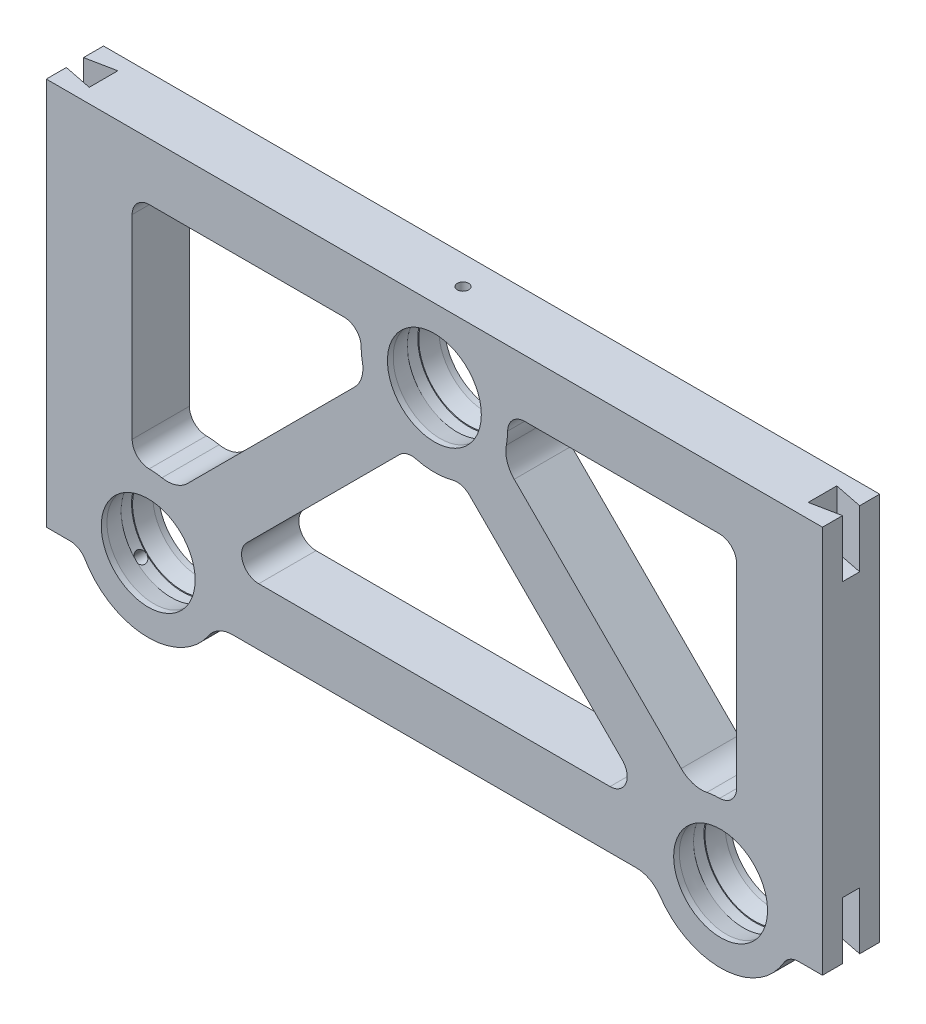
SolidWorks part; units mm, degrees
ref_plane "Front Plane" through (0, 0, 0) normal (0, 0, 1) x (1, 0, 0)
ref_plane "Top Plane" through (0, 0, 0) normal (0, 1, 0) x (1, 0, 0)
ref_plane "Right Plane" through (0, 0, 0) normal (1, 0, 0) x (0, 0, -1)
sketch "Sketch1" plane through (0, 0, 0) normal (0, 0, 1) x (1, 0, 0)
  line L0 (-26.538, 0) -> (73.462, 0) construction
  line L2 (-26.538, 0) -> (23.462, 50) construction
  line L3 (23.462, 50) -> (73.462, 0) construction
  line L4 (-14.755, 5) -> (61.679, 5)
  line L5 (-14.755, -5) -> (61.679, -5)
  line L6 (-21.7417, 11.8674) -> (11.5946, 45.2037)
  line L7 (18.6657, 38.1326) -> (-14.6706, 4.7963)
  line L8 (28.2583, 38.1326) -> (61.5946, 4.7963)
  line L9 (35.3294, 45.2037) -> (68.6657, 11.8674)
  circle A0 centre (23.462, 50) radius 8.2
  circle A1 centre (73.462, 0) radius 8.2
  circle A2 centre (-26.538, 0) radius 8.2
  circle A3 centre (-26.538, 0) radius 12.8
  circle A4 centre (23.462, 50) radius 12.8
  circle A5 centre (73.462, 0) radius 12.8
  dimension "D1" = 16.4
  dimension "D2" = 16.4
  dimension "D3" = 16.4
  dimension "D4" = 45
  dimension "D5" = 45
  dimension "D6" = 100
  dimension "D7" = 4.6
  dimension "D8" = 4.6
  dimension "D9" = 4.6
  dimension "D10" = 5
  dimension "D11" = 5
  dimension "D12" = 5
  dimension "D13" = 5
  dimension "D14" = 5
  dimension "D15" = 5
extrude "Boss-Extrude1" add sketch "Sketch1" along normal blind 8 contours A3 A2 | A4 L6 A3 L4 L7 | A4 A0 | A5 L9 A4 L8 L4 | A5 L8 L4 L7 A3 L5 | A5 A1 | A3 L7 L4 | A5 L4 L8
sketch3d "3DSketch1" plane through (0, 0, 0) normal (0, 0, 1) x (1, 0, 0)
  dimension "D1" = 4
sketch "Sketch3" plane through (0, 0, 4) normal (0, 0, 1) x (1, 0, 0)
  circle A0 centre (-26.538, 0) radius 8.9053
  circle A1 centre (23.462, 50) radius 8.9053
  circle A2 centre (73.462, 0) radius 8.9053
  circle A3 centre (-26.538, 0) radius 8.2 construction
  circle A4 centre (23.462, 50) radius 8.2 construction
  circle A5 centre (73.462, 0) radius 8.2 construction
  dimension "D1" = 0.7053
  dimension "D2" = 0.7053
  dimension "D3" = 0.7053
extrude "Cut-Extrude1" cut sketch "Sketch3" against normal blind 1 and the other way blind 1 contours A1 | A0 | A2
sketch3d "3DSketch2" plane through (0, 0, 0) normal (0, 0, 1) x (1, 0, 0)
sketch3d "3DSketch3" plane through (0, 0, 0) normal (0, 0, 1) x (1, 0, 0)
  dimension "D1" = 26
sketch "Sketch4" plane through (0, 63.2, 0) normal (0, -1, 0) x (-1, 0, 0)
  line L0 (-41.8, -4) -> (41.8, -4) construction
  line L1 (-86.262, 0) -> (-86.262, -8) construction
  line L4 (-36.2617, -8) -> (-68.6657, -8)
  line L5 (-36.2617, -8) -> (-68.6657, -8)
  line L6 (-68.6657, -8) -> (-86.262, -8)
  line L7 (-68.6657, -8) -> (-86.262, -8)
  line L8 (-86.262, -8) -> (-86.262, 0)
  line L9 (-86.262, -8) -> (-86.262, 0)
  line L10 (-86.262, 0) -> (-68.6657, 0)
  line L11 (-86.262, 0) -> (-68.6657, 0)
  line L12 (-68.6657, 0) -> (-36.2617, 0)
  line L13 (-68.6657, 0) -> (-36.2617, 0)
  line L14 (-36.2617, 0) -> (-10.6623, 0)
  line L15 (-36.2617, 0) -> (-10.6623, 0)
  line L16 (-10.6623, 0) -> (21.7417, 0)
  line L17 (-10.6623, 0) -> (21.7417, 0)
  line L18 (21.7417, 0) -> (39.338, 0)
  line L19 (21.7417, 0) -> (39.338, 0)
  line L20 (39.338, 0) -> (39.338, -8)
  line L21 (39.338, 0) -> (39.338, -8)
  line L22 (39.338, -8) -> (21.7417, -8)
  line L23 (39.338, -8) -> (21.7417, -8)
  line L24 (21.7417, -8) -> (-10.6623, -8)
  line L25 (21.7417, -8) -> (-10.6623, -8)
  line L26 (-10.6623, -8) -> (-36.2617, -8)
  line L27 (-10.6623, -8) -> (-36.2617, -8)
  circle A0 centre (-23.462, -4) radius 1
  dimension "D1" = 2
  dimension "D2" = 62.8
  dimension "D3" = 125.6
extrude "Cut-Extrude2" cut sketch "Sketch4" along normal blind 6 and the other way blind 8 contours A0
fillet "Fillet1" radius 3 4 edges at (-14.4669, 5, 4) (18.6657, 38.1326, 4) (28.2583, 38.1326, 4) (61.3909, 5, 4)
fillet "Fillet2" radius 5 6 edges at (68.6657, 11.8674, 4) (35.3294, 45.2037, 4) (11.5946, 45.2037, 4) (-21.7417, 11.8674, 4) (-14.755, -5, 4) (61.679, -5, 4)
sketch3d "3DSketch4" plane through (0, 0, 0) normal (0, 0, 1) x (1, 0, 0)
sketch3d "3DSketch5" plane through (0, 0, 0) normal (0, 0, 1) x (1, 0, 0)
  dimension "D1" = 26
sketch "Sketch5" plane through (46.0648, -46.0648, 0) normal (-0.7071, 0.7071, 0) x (0, 0, 1)
  line L0 (8, -31.5652) -> (8, -8.1761) construction
  line L1 (8, 43.7455) -> (8, 60.1455) construction
  line L2 (8, 43.7455) -> (8, 60.1455)
  line L7 (8, 64.7455) -> (0, 64.7455) construction
  line L8 (8, 64.7455) -> (0, 64.7455)
  circle A0 centre (4, 51.9455) radius 1
  dimension "D1" = 2
  dimension "D2" = 4
  dimension "D3" = 8.2
  dimension "D4" = 16.4
extrude "Cut-Extrude3" cut sketch "Sketch5" along normal blind 10 and the other way blind 8 contours A0
draft "Draft4" type of draft neutral plane draft angle 10 faces to draft 3 face at (-18.338, 0, 5) face at (31.662, 50, 5) face at (81.662, 0, 5) neutral plane through (0, 0, 8) neutral plane normal (0, 0, 1) reverse direction yes parameters "D1"=10
draft "Draft6" type of draft neutral plane draft angle 10 faces to draft 3 face at (-18.338, 0, 0) face at (81.662, 0, 0) face at (31.662, 50, 0) neutral plane through (0, 0, 0) neutral plane normal (0, 0, -1) reverse direction yes parameters "D1"=10
sketch3d "3DSketch6" plane through (0, 0, 0) normal (0, 0, 1) x (1, 0, 0)
sketch3d "3DSketch8" plane through (0, 0, 0) normal (0, 0, 1) x (1, 0, 0)
  dimension "D1" = 26
sketch "Sketch6" plane through (-22.6028, -22.6028, 0) normal (0.7071, 0.7071, 0) x (0, 0, -1)
  line L0 (-8, 31.5652) -> (-8, 5.9652) construction
  line L1 (0, 31.5652) -> (-8, 31.5652) construction
  line L2 (0, 31.5652) -> (-8, 31.5652)
  line L3 (0, 10.5652) -> (0, 26.9652) construction
  line L4 (0, 10.5652) -> (0, 26.9652)
  circle A0 centre (-4, 18.7652) radius 1
  dimension "D1" = 2
  dimension "D2" = 4
  dimension "D4" = 16.4
  dimension "D5" = 8.2
extrude "Cut-Extrude4" cut sketch "Sketch6" along normal blind 10 and the other way blind 8 contours A0
sketch "Sketch7" plane through (0, 0, 8) normal (0, 0, 1) x (1, 0, 0)
  line L2 (-7.2243, 5) -> (54.1483, 5) construction
  line L5 (17.3632, 36.8302) -> (-9.3456, 10.1213) construction
  line L10 (29.5608, 36.8302) -> (56.2696, 10.1213) construction
  line L11 (66.585, 13.948) -> (37.41, 43.123)
  line L12 (9.514, 43.123) -> (-19.661, 13.948)
  line L13 (-11.8125, -5) -> (58.7365, -5)
  line L14 (66.585, 13.948) -> (37.41, 43.123)
  line L15 (9.514, 43.123) -> (-19.661, 13.948)
  line L16 (-11.8125, -5) -> (58.7365, -5)
  line L17 (-7.2243, 5) -> (54.1483, 5)
  line L18 (17.3632, 36.8302) -> (-9.3456, 10.1213)
  line L19 (29.5608, 36.8302) -> (56.2696, 10.1213)
  circle A36 centre (-26.538, 0) radius 8.2 construction
  arc A37 (-9.3456, 10.1213) -> (-7.2243, 5) centre (-7.2243, 8) ccw construction
  arc A38 (54.1483, 5) -> (56.2696, 10.1213) centre (54.1483, 8) ccw construction
  circle A39 centre (73.462, 0) radius 8.2 construction
  circle A40 centre (23.462, 50) radius 8.2 construction
  arc A41 (29.5608, 36.8302) -> (26.6842, 37.6122) centre (27.4395, 34.7088) ccw construction
  arc A42 (20.2398, 37.6122) -> (26.6842, 37.6122) centre (23.462, 50) ccw construction
  arc A43 (20.2398, 37.6122) -> (17.3632, 36.8302) centre (19.4845, 34.7088) ccw construction
  circle A44 centre (-26.538, 0) radius 8.2
  arc A45 (36.0344, 47.5972) -> (37.41, 43.123) centre (40.9456, 46.6586) ccw
  arc A46 (36.0344, 47.5972) -> (10.8895, 47.5972) centre (23.462, 50) ccw
  arc A47 (9.514, 43.123) -> (10.8895, 47.5972) centre (5.9784, 46.6586) ccw
  arc A48 (-24.1352, 12.5724) -> (-19.661, 13.948) centre (-23.1966, 17.4836) ccw
  arc A49 (-24.1352, 12.5724) -> (-15.9489, -7.191) centre (-26.538, 0) ccw
  arc A50 (-11.8125, -5) -> (-15.9489, -7.191) centre (-11.8125, -10) ccw
  arc A51 (62.8729, -7.191) -> (58.7365, -5) centre (58.7365, -10) ccw
  arc A52 (62.8729, -7.191) -> (71.0592, 12.5724) centre (73.462, 0) ccw
  arc A53 (66.585, 13.948) -> (71.0592, 12.5724) centre (70.1206, 17.4836) ccw
  arc A54 (36.0344, 47.5972) -> (37.41, 43.123) centre (40.9456, 46.6586) ccw
  arc A55 (36.0344, 47.5972) -> (10.8895, 47.5972) centre (23.462, 50) ccw
  arc A56 (9.514, 43.123) -> (10.8895, 47.5972) centre (5.9784, 46.6586) ccw
  arc A57 (-24.1352, 12.5724) -> (-19.661, 13.948) centre (-23.1966, 17.4836) ccw
  arc A58 (-24.1352, 12.5724) -> (-15.9489, -7.191) centre (-26.538, 0) ccw
  arc A59 (-11.8125, -5) -> (-15.9489, -7.191) centre (-11.8125, -10) ccw
  arc A60 (62.8729, -7.191) -> (58.7365, -5) centre (58.7365, -10) ccw
  arc A61 (62.8729, -7.191) -> (71.0592, 12.5724) centre (73.462, 0) ccw
  arc A62 (66.585, 13.948) -> (71.0592, 12.5724) centre (70.1206, 17.4836) ccw
  arc A63 (-9.3456, 10.1213) -> (-7.2243, 5) centre (-7.2243, 8) ccw
  arc A64 (54.1483, 5) -> (56.2696, 10.1213) centre (54.1483, 8) ccw
  circle A65 centre (73.462, 0) radius 8.2
  circle A66 centre (23.462, 50) radius 8.2
  arc A67 (29.5608, 36.8302) -> (26.6842, 37.6122) centre (27.4395, 34.7088) ccw
  arc A68 (20.2398, 37.6122) -> (26.6842, 37.6122) centre (23.462, 50) ccw
  arc A69 (20.2398, 37.6122) -> (17.3632, 36.8302) centre (19.4845, 34.7088) ccw
  dimension "D1" = 0
extrude "Boss-Extrude3" add sketch "Sketch7" along normal blind 1
sketch "Sketch11" plane through (0, 0, 0) normal (0, 0, -1) x (-1, 0, 0)
  line L0 (-29.5608, 36.8302) -> (-56.2696, 10.1213) construction
  line L1 (7.2243, 5) -> (-54.1483, 5) construction
  line L2 (-17.3632, 36.8302) -> (9.3456, 10.1213) construction
  line L3 (-37.41, 43.123) -> (-66.585, 13.948)
  line L4 (-58.7365, -5) -> (11.8125, -5)
  line L5 (19.661, 13.948) -> (-9.514, 43.123)
  line L6 (-37.41, 43.123) -> (-66.585, 13.948)
  line L7 (-58.7365, -5) -> (11.8125, -5)
  line L8 (19.661, 13.948) -> (-9.514, 43.123)
  line L9 (-17.3632, 36.8302) -> (9.3456, 10.1213)
  line L10 (7.2243, 5) -> (-54.1483, 5)
  line L11 (-29.5608, 36.8302) -> (-56.2696, 10.1213)
  circle A0 centre (-23.462, 50) radius 8.2 construction
  circle A1 centre (-73.462, 0) radius 8.2
  circle A2 centre (-73.462, 0) radius 8.2
  circle A3 centre (-23.462, 50) radius 8.2
  circle A4 centre (26.538, 0) radius 8.2 construction
  circle A5 centre (26.538, 0) radius 8.2
  arc A6 (-17.3632, 36.8302) -> (-20.2398, 37.6122) centre (-19.4845, 34.7088) ccw construction
  arc A7 (-26.6842, 37.6122) -> (-20.2398, 37.6122) centre (-23.462, 50) ccw construction
  arc A8 (-26.6842, 37.6122) -> (-29.5608, 36.8302) centre (-27.4395, 34.7088) ccw construction
  arc A9 (-56.2696, 10.1213) -> (-54.1483, 5) centre (-54.1483, 8) ccw construction
  arc A10 (7.2243, 5) -> (9.3456, 10.1213) centre (7.2243, 8) ccw construction
  arc A11 (-10.8895, 47.5972) -> (-36.0344, 47.5972) centre (-23.462, 50) ccw
  arc A12 (-37.41, 43.123) -> (-36.0344, 47.5972) centre (-40.9456, 46.6586) ccw
  arc A13 (-71.0592, 12.5724) -> (-66.585, 13.948) centre (-70.1206, 17.4836) ccw
  arc A14 (-71.0592, 12.5724) -> (-62.8729, -7.191) centre (-73.462, 0) ccw
  arc A15 (-58.7365, -5) -> (-62.8729, -7.191) centre (-58.7365, -10) ccw
  arc A16 (15.9489, -7.191) -> (11.8125, -5) centre (11.8125, -10) ccw
  arc A17 (15.9489, -7.191) -> (24.1352, 12.5724) centre (26.538, 0) ccw
  arc A18 (19.661, 13.948) -> (24.1352, 12.5724) centre (23.1966, 17.4836) ccw
  arc A19 (-10.8895, 47.5972) -> (-9.514, 43.123) centre (-5.9784, 46.6586) ccw
  arc A20 (-10.8895, 47.5972) -> (-36.0344, 47.5972) centre (-23.462, 50) ccw
  arc A21 (-37.41, 43.123) -> (-36.0344, 47.5972) centre (-40.9456, 46.6586) ccw
  arc A22 (-71.0592, 12.5724) -> (-66.585, 13.948) centre (-70.1206, 17.4836) ccw
  arc A23 (-71.0592, 12.5724) -> (-62.8729, -7.191) centre (-73.462, 0) ccw
  arc A24 (-58.7365, -5) -> (-62.8729, -7.191) centre (-58.7365, -10) ccw
  arc A25 (15.9489, -7.191) -> (11.8125, -5) centre (11.8125, -10) ccw
  arc A26 (15.9489, -7.191) -> (24.1352, 12.5724) centre (26.538, 0) ccw
  arc A27 (19.661, 13.948) -> (24.1352, 12.5724) centre (23.1966, 17.4836) ccw
  arc A28 (-10.8895, 47.5972) -> (-9.514, 43.123) centre (-5.9784, 46.6586) ccw
  arc A29 (7.2243, 5) -> (9.3456, 10.1213) centre (7.2243, 8) ccw
  arc A30 (-56.2696, 10.1213) -> (-54.1483, 5) centre (-54.1483, 8) ccw
  arc A31 (-26.6842, 37.6122) -> (-29.5608, 36.8302) centre (-27.4395, 34.7088) ccw
  arc A32 (-26.6842, 37.6122) -> (-20.2398, 37.6122) centre (-23.462, 50) ccw
  arc A33 (-17.3632, 36.8302) -> (-20.2398, 37.6122) centre (-19.4845, 34.7088) ccw
  dimension "D1" = 0
  dimension "D2" = 0
extrude "Boss-Extrude4" add sketch "Sketch11" along normal blind 1
sketch "Sketch12" plane through (0, 0, 9) normal (0, 0, 1) x (1, 0, 0)
  line L1 (-39.338, -12.8) -> (-60.338, -12.8)
  line L2 (-39.338, -12.8) -> (-39.338, 62.8)
  line L3 (-39.338, 62.8) -> (-60.338, 62.8)
  line L4 (-60.338, -12.8) -> (-60.338, 62.8)
  arc A0 (-24.1352, 12.5724) -> (-15.9489, -7.191) centre (-26.538, 0) ccw construction
  arc A1 (36.0344, 47.5972) -> (10.8895, 47.5972) centre (23.462, 50) ccw construction
  dimension "D1" = 21
extrude "Boss-Extrude5" add sketch "Sketch12" against normal blind 10 separate body
sketch "Sketch13" plane through (0, 0, 9) normal (0, 0, 1) x (1, 0, 0)
  line L0 (-60.338, 62.8) -> (-60.338, -12.8) construction
  line L1 (-60.338, 52.8) -> (-39.338, 52.8)
  line L2 (-60.338, 52.8) -> (-60.338, 5)
  line L3 (-60.338, 5) -> (-39.338, 5)
  line L4 (-39.338, 52.8) -> (-39.338, 5)
  line L5 (-39.338, -12.8) -> (-39.338, 62.8) construction
  line L6 (-39.338, 62.8) -> (-60.338, 62.8) construction
  line L7 (-11.8125, -5) -> (58.7365, -5) construction
  line L9 (-60.338, -5) -> (-39.338, -5)
  line L10 (-60.338, -5) -> (-60.338, -12.8)
  line L11 (-60.338, -12.8) -> (-39.338, -12.8)
  line L12 (-39.338, -5) -> (-39.338, -12.8)
  dimension "D1" = 10
  dimension "D2" = 10
extrude "Cut-Extrude6" cut sketch "Sketch13" against normal blind 25
sketch "Sketch14" plane through (0, 62.8, 0) normal (0, 1, 0) x (1, 0, 0)
  line L0 (-18.338, 1) -> (-34.738, 1) construction
  line L1 (-39.338, -9) -> (-29.338, -9)
  line L2 (-39.338, -9) -> (-39.338, 1)
  line L3 (-39.338, 1) -> (-29.338, 1)
  line L4 (-29.338, -9) -> (-29.338, 1)
  dimension "D1" = 10
extrude "Boss-Extrude6" add sketch "Sketch14" against normal up to surface (62.8 mm away)
sketch "Sketch15" plane through (0, -5, 0) normal (0, -1, 0) x (1, 0, 0)
  line L0 (-39.338, -1) -> (-15.9489, -1) construction
  line L1 (-39.338, 9) -> (-36.838, 9)
  line L2 (-39.338, 9) -> (-39.338, -1)
  line L3 (-39.338, -1) -> (-36.838, -1)
  line L4 (-36.838, 9) -> (-36.838, -1)
  dimension "D1" = 2.5
extrude "Boss-Extrude8" add sketch "Sketch15" against normal blind 6
sketch "Sketch17" plane through (-29.338, 0, 0) normal (1, 0, 0) x (0, 0, -1)
  line L0 (1, 47.5972) -> (1, 62.8) construction
  line L1 (-9, 62.8) -> (1, 62.8)
  line L2 (-9, 62.8) -> (-9, 52.8)
  line L3 (-9, 52.8) -> (1, 52.8)
  line L4 (1, 62.8) -> (1, 52.8)
  dimension "D1" = 10
extrude "Boss-Extrude9" add sketch "Sketch17" along normal up to surface (52.8 mm away) up to face at (23.462, 37.4061, 4)
sketch "Sketch20" plane through (0, 62.8, 0) normal (0, 1, 0) x (1, 0, 0)
  line L0 (-60.338, -9) -> (23.462, -9) construction
  line L1 (-60.338, 1) -> (-44.338, 1)
  line L2 (-60.338, 1) -> (-60.338, -9)
  line L3 (-60.338, -9) -> (-44.338, -9)
  line L4 (-44.338, 1) -> (-44.338, -9)
  line L6 (-44.338, -2.5) -> (-39.338, -1.5)
  line L7 (-39.338, -1.5) -> (-39.338, -6.5)
  line L8 (-39.338, -6.5) -> (-44.338, -5.5)
  line L9 (-44.338, -4) -> (-39.338, -4) construction
  line L10 (-39.338, 1) -> (-39.338, -9) construction
  line M7 (23.462, 1) -> (-60.338, 1)
  line M8 (-60.338, 1) -> (-60.338, -9)
  line M9 (-60.338, -9) -> (23.462, -9)
  dimension "D1" = 5
  dimension "D2" = 5
  dimension "D3" = 3
extrude "Cut-Extrude8" cut sketch "Sketch20" along direction (0, 1, 0) on the side against the normal blind 10 contours L4 M7 M8 M9 | L4 L9 L7 L6 | L9 L4 L8 L7
sketch "Sketch22" plane through (0, 0, 9) normal (0, 0, 1) x (1, 0, 0)
  line L0 (-38.321, -5) -> (-60.338, -5) construction
  line L1 (-44.338, 52.8) -> (-39.338, 52.8)
  line L2 (-44.338, 52.8) -> (-44.338, -5)
  line L3 (-44.338, -5) -> (-39.338, -5)
  line L4 (-39.338, 52.8) -> (-39.338, -5)
  line L5 (-39.338, 5) -> (-39.338, 52.8) construction
extrude "Boss-Extrude10" add sketch "Sketch22" against normal blind 10
sketch "Sketch23" plane through (0, -5, 0) normal (0, -1, 0) x (1, 0, 0)
  line L0 (-38.321, -1) -> (-60.338, -1) construction
  line L1 (-60.338, 9) -> (-44.338, 9)
  line L2 (-60.338, 9) -> (-60.338, -1)
  line L3 (-60.338, -1) -> (-44.338, -1)
  line L4 (-44.338, 9) -> (-44.338, -1)
  line L5 (-44.338, 5.5) -> (-39.338, 6.5)
  line L6 (-39.338, 6.5) -> (-39.338, 1.5)
  line L7 (-39.338, 1.5) -> (-44.338, 2.5)
  line L8 (-44.338, 4) -> (-39.338, 4) construction
  line L11 (-44.338, 5.5) -> (-44.338, 9) construction
  line M9 (-38.321, 9) -> (-60.338, 9)
  line M10 (-60.338, 9) -> (-60.338, -1)
  line M11 (-60.338, -1) -> (-38.321, -1)
  line M12 (-38.321, -1) -> (-38.321, 9)
  dimension "D1" = 5
  dimension "D2" = 5
  dimension "D3" = 3
extrude "Cut-Extrude9" cut sketch "Sketch23" against normal blind 10 contours L4 M9 M10 M11 | L4 L8 L6 L5 | L8 L4 L7 M12
sketch "Sketch24" plane through (0, 62.8, 0) normal (0, 1, 0) x (1, 0, 0)
  line L0 (23.462, -3) -> (23.462, -5) construction
  circle A0 centre (23.462, -4) radius 1
  arc A1 (23.462, -5) -> (23.462, -3) centre (23.462, -4) ccw construction
extrude "Cut-Extrude10" cut sketch "Sketch24" against normal blind 10
sketch "Sketch26" plane through (0, 0, 9) normal (0, 0, 1) x (1, 0, 0)
  line L1 (23.462, 66.2004) -> (104.7821, 66.2004)
  line L2 (23.462, 66.2004) -> (23.462, -14.8495)
  line L3 (23.462, -14.8495) -> (104.7821, -14.8495)
  line L4 (104.7821, 66.2004) -> (104.7821, -14.8495)
  circle A1 centre (23.462, 50) radius 8.2 construction
  point P6 (23.462, 50)
extrude "Cut-Extrude12" cut sketch "Sketch26" against normal blind 10
mirror "Mirror3" about plane through (23.462, 66.2004, -1) normal (-1, 0, 0) of bodies 129
fillet "Fillet3" radius 3 8 edges at (-38.321, -5, 4) (85.245, -5, 4) (-29.338, 12.49, 4) (76.262, 12.49, 4) (76.262, 52.8, 4) (-29.338, 52.8, 4) (35.952, 52.8, 4) (10.972, 52.8, 4)
equation "\"D2@Sketch1\"=\"D1@Sketch1\""
equation "\"D3@Sketch1\"=\"D1@Sketch1\""
equation "\"D5@Sketch1\"=\"D4@Sketch1\""
equation "\"D8@Sketch1\"=\"D7@Sketch1\""
equation "\"D9@Sketch1\"=\"D7@Sketch1\""
equation "\"D11@Sketch1\"=\"D10@Sketch1\""
equation "\"D12@Sketch1\"=\"D10@Sketch1\""
equation "\"D13@Sketch1\"=\"D10@Sketch1\""
equation "\"D14@Sketch1\"=\"D13@Sketch1\""
equation "\"D15@Sketch1\"=\"D14@Sketch1\""
equation "\"D2@Sketch3\"=\"D1@Sketch3\""
equation "\"D3@Sketch3\"=\"D1@Sketch3\""
equation "\"D2@Sketch4\"=\"D3@Sketch4\"/2"
equation "\"D3@Sketch5\"=\"D4@Sketch5\"/2"
equation "\"D2@Sketch5\"=\"D5@Sketch5\"/2"
equation "\"D2@Sketch6\"=\"D3@Sketch6\"/2"
equation "\"D5@Sketch6\"=\"D4@Sketch6\"/2"
equation "\"D1@Sketch3\"=4*tan(10)"
equation "\"D7@Sketch1\"=21-\"D1@Sketch1\""
